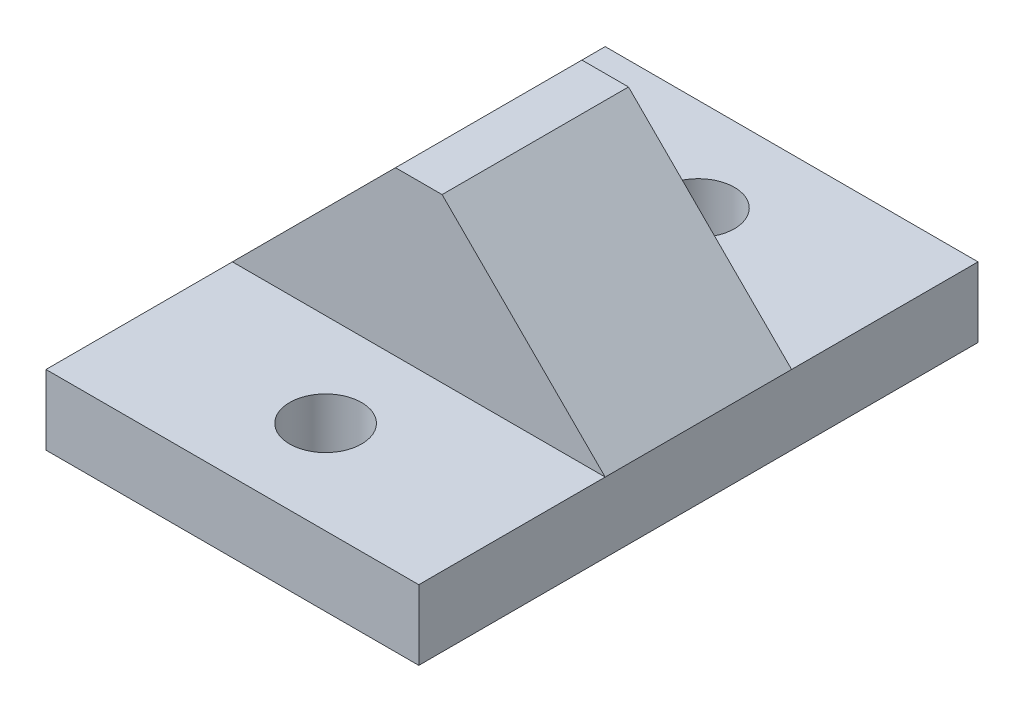
SolidWorks part; units mm, degrees
material "6061-T6 (SS)"
ref_plane "Front" through (0, 0, 0) normal (0, 0, 1) x (1, 0, 0)
ref_plane "Top" through (0, 0, 0) normal (0, 1, 0) x (1, 0, 0)
ref_plane "Right" through (0, 0, 0) normal (1, 0, 0) x (0, 0, -1)
sketch "Sketch1" plane through (0, 0, 0) normal (0, 0, 1) x (1, 0, 0)
  line L0 (0, 0) -> (25.4, 0)
  line L1 (50, 0) -> (-50, 0) construction
  line L2 (25.4, 0) -> (25.4, 9.525)
  line L3 (-25.4, 9.525) -> (-3.175, 31.75)
  line L4 (-3.175, 31.75) -> (3.175, 31.75)
  line L6 (3.175, 31.75) -> (25.4, 9.525)
  line L7 (0, 31.75) -> (0, 0) construction
  line L8 (-25.4, 9.525) -> (-25.4, 0)
  line L9 (-25.4, 0) -> (0, 0)
  point P5 (0, 31.75)
  dimension "D1" = 50.8
  dimension "D2" = 6.35
  dimension "D3" = 31.75
  dimension "D4" = 90
extrude "Boss-Extrude1" add sketch "Sketch1" along normal mid plane 76.2
sketch "Sketch6" plane through (0, 0, 38.1) normal (0, 0, 1) x (1, 0, 0)
  line L0 (-25.4, 9.525) -> (25.4, 9.525)
  line L1 (25.4, 9.525) -> (3.175, 31.75)
  line L3 (3.175, 31.75) -> (-3.175, 31.75)
  line L4 (-3.175, 31.75) -> (-25.4, 9.525)
extrude "Cut-Extrude2" cut sketch "Sketch6" against normal blind 25.4
sketch "Sketch7" plane through (0, 9.525, 0) normal (0, 1, 0) x (1, 0, 0)
  line L0 (0, -12.7) -> (0, -25.4) construction
  line L2 (-25.4, -12.7) -> (25.4, -12.7) construction
  dimension "D1" = 12.7
hole_wizard "3/8 Clearance Hole2" positions "Sketch9" profile "Sketch8" hole size "3/8" standard "ANSI Inch" end condition through all
sketch "Sketch9" plane through (0, 9.525, 0) normal (0, 1, 0) x (1, 0, 0)
  point P0 (0, -25.4)
sketch "Sketch8" plane through (0, 9.525, 25.4) normal (1, 0, 0) x (0, 0, 1)
  line L0 (0, 0) -> (0, 9.525)
  line L1 (0, 9.525) -> (4.9022, 9.525)
  line L2 (4.9022, 9.525) -> (4.9022, 0)
  line L5 (4.9022, 0) -> (0, 0)
  line L11 (0, -6.35) -> (0, 107.95) construction
  dimension "Thru Hole Dia." = 9.8044
  dimension "Thru Hole Depth" = 9.525
mirror "Mirror2" about plane through (0, 0, 0) normal (0, 0, 1) of "3/8 Clearance Hole2", "Cut-Extrude2"
